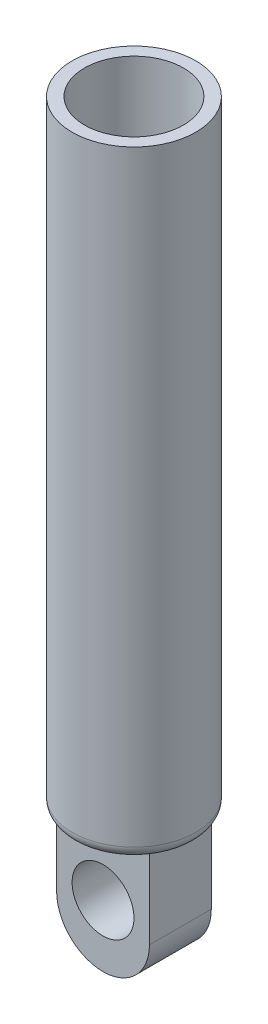
SolidWorks part; units mm, degrees
ref_plane "Front Plane" through (0, 0, 0) normal (0, 0, 1) x (1, 0, 0)
ref_plane "Top Plane" through (0, 0, 0) normal (0, 1, 0) x (1, 0, 0)
ref_plane "Right Plane" through (0, 0, 0) normal (1, 0, 0) x (0, 0, -1)
sketch "Sketch1" plane through (0, 0, 0) normal (0, 1, 0) x (1, 0, 0)
  circle A0 centre (0, 0) radius 10
  dimension "D1" = 20
extrude "Boss-Extrude1" add sketch "Sketch1" along normal blind 100
shell "Shell1" thickness 2 removed face at (0, 100, 10)
fillet "Fillet1" radius 2 1 edges at (0, 0, 10)
sketch "Sketch2" plane through (0, 0, 0) normal (0, -1, 0) x (1, 0, 0)
  line L1 (-7.5, -5) -> (7.5, -5)
  line L2 (-7.5, -5) -> (-7.5, 5)
  line L3 (-7.5, 5) -> (7.5, 5)
  line L4 (7.5, -5) -> (7.5, 5)
  line L5 (-7.5, -5) -> (7.5, 5) construction
  line L6 (-7.5, 5) -> (7.5, -5) construction
  point P0 (0, 0)
  dimension "D1" = 10
  dimension "D2" = 15
extrude "Boss-Extrude2" add sketch "Sketch2" along normal blind 20 and the other way blind 1
sketch "Sketch3" plane through (0, 0, 5) normal (0, 0, 1) x (1, 0, 0)
  line L0 (7.5, -20) -> (-7.5, -20) construction
  line L1 (7.5, 0.276) -> (7.5, -20) construction
  circle A0 centre (0, -10) radius 5
  dimension "D1" = 10
  dimension "D2" = 10
  dimension "D3" = 7.5
extrude "Cut-Extrude1" cut sketch "Sketch3" against normal blind 20
fillet "Fillet2" radius 7.5 2 edges at (7.5, -20, 0) (-7.5, -20, 0)
